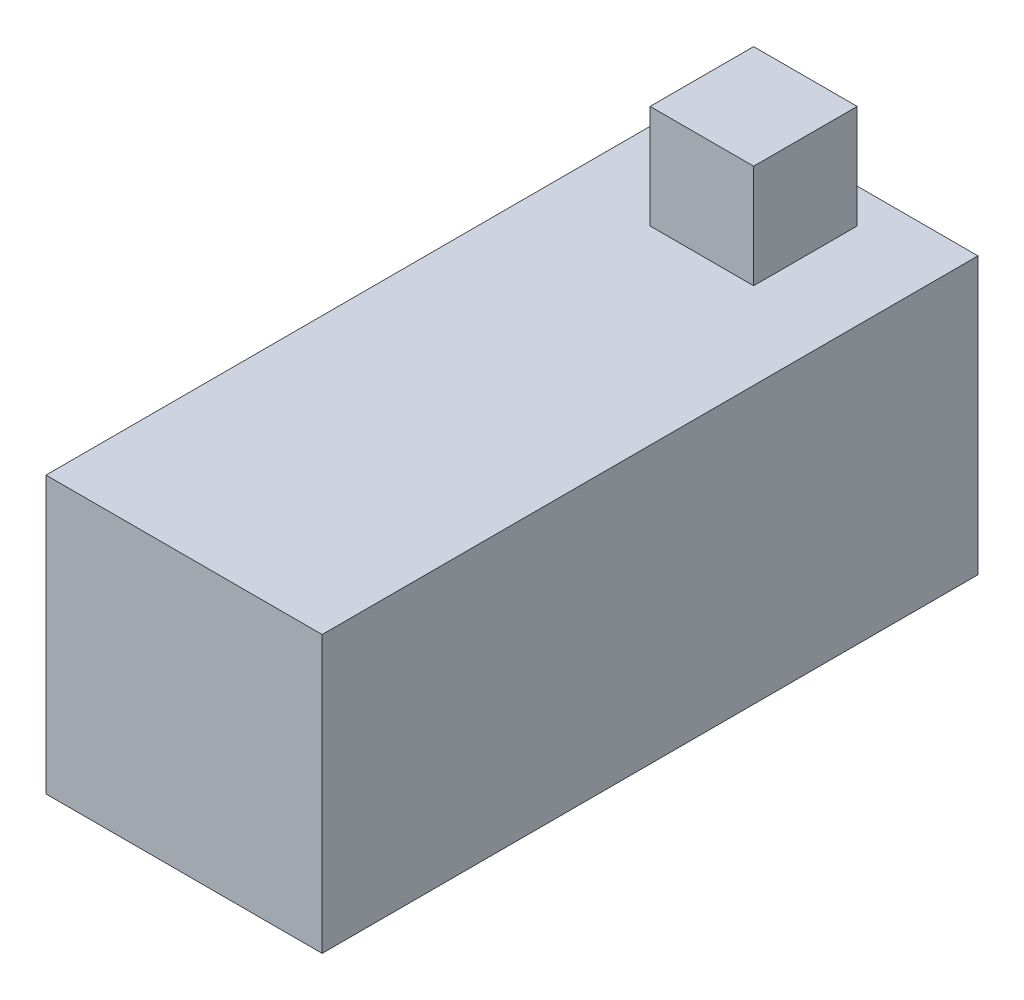
SolidWorks part; units mm, degrees
ref_plane "Front Plane" through (0, 0, 0) normal (0, 0, 1) x (1, 0, 0)
ref_plane "Top Plane" through (0, 0, 0) normal (0, 1, 0) x (1, 0, 0)
ref_plane "Right Plane" through (0, 0, 0) normal (1, 0, 0) x (0, 0, -1)
sketch "Sketch2" plane through (0, 0, 0) normal (0, 1, 0) x (1, 0, 0)
  line L1 (-4, -9.5) -> (4, -9.5)
  line L2 (-4, -9.5) -> (-4, 9.5)
  line L3 (-4, 9.5) -> (4, 9.5)
  line L4 (4, -9.5) -> (4, 9.5)
  line L5 (-4, -9.5) -> (4, 9.5) construction
  line L6 (-4, 9.5) -> (4, -9.5) construction
  line L7 (-1.5, 8.5) -> (1.5, 8.5)
  line L8 (-1.5, 8.5) -> (-1.5, 5.5)
  line L9 (-1.5, 5.5) -> (1.5, 5.5)
  line L10 (1.5, 8.5) -> (1.5, 5.5)
  line L11 (-1.5, 8.5) -> (1.5, 5.5) construction
  line L12 (-1.5, 5.5) -> (1.5, 8.5) construction
  point P0 (0, 0)
  point P6 (0, 7)
  point P11 (0, 8.5)
  dimension "D1" = 19
  dimension "D2" = 8
  dimension "D3" = 3
  dimension "D4" = 3
  dimension "D5" = 1
extrude "Boss-Extrude1" add sketch "Sketch2" against normal blind 8 contours L10 L7 L8 L9 | L1 L4 L3 L2 L7 L10 L9 L8 region at (0, 0, 0.4406) region at (0, 0, -7)
extrude "Boss-Extrude2" add sketch "Sketch2<3>" along normal blind 3 contours L10 L7 L8 L9 region at (0, 0, -7)
sketch "Sketch2<3>" plane through (0, 0, 0) normal (0, 1, 0) x (1, 0, 0) same geometry as "Sketch2"
sketch "Sketch3" plane through (0, 0, -9.5) normal (0, 0, -1) x (-1, 0, 0)
  line L0 (4, -8) -> (-4, -8) construction
  circle A0 centre (0, -4) radius 3.5
  dimension "D1" = 7
  dimension "D2" = 4
extrude "Cut-Extrude1" cut sketch "Sketch3" against normal blind 1 contours A0
